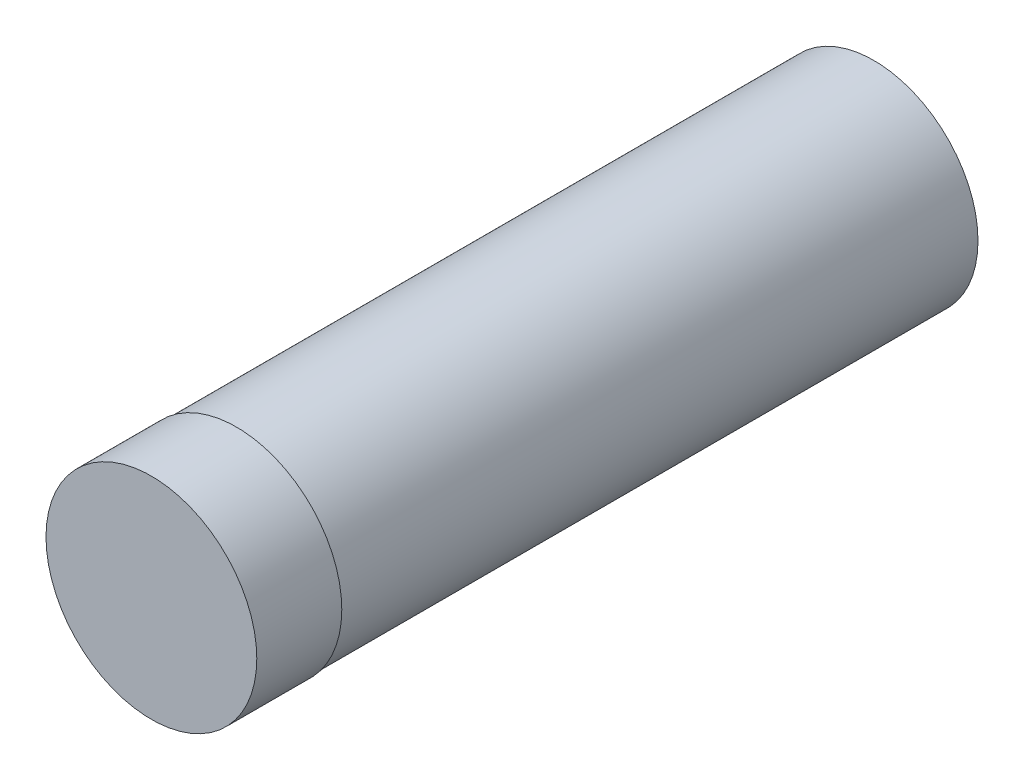
SolidWorks part; units mm, degrees
ref_plane "Front Plane" through (0, 0, 0) normal (0, 0, 1) x (1, 0, 0)
ref_plane "Top Plane" through (0, 0, 0) normal (0, 1, 0) x (1, 0, 0)
ref_plane "Right Plane" through (0, 0, 0) normal (1, 0, 0) x (0, 0, -1)
sketch "Sketch1" plane through (0, 0, 0) normal (0, 0, 1) x (1, 0, 0)
  circle A0 centre (0, 0) radius 2.45
  dimension "D1" = 4.9
extrude "Boss-Extrude1" add sketch "Sketch1" along normal mid plane 17
sketch "Sketch2" plane through (0, 0, 0) normal (0, 0, 1) x (1, 0, 0)
  circle A0 centre (0, 0) radius 2.5 construction
  dimension "D1" = 5
sketch "Sketch3" plane through (0, 0, 8.5) normal (0, 0, 1) x (1, 0, 0)
  circle A0 centre (0, 0) radius 2.48
  dimension "D1" = 4.96
extrude "Boss-Extrude2" add sketch "Sketch3" against normal blind 2
